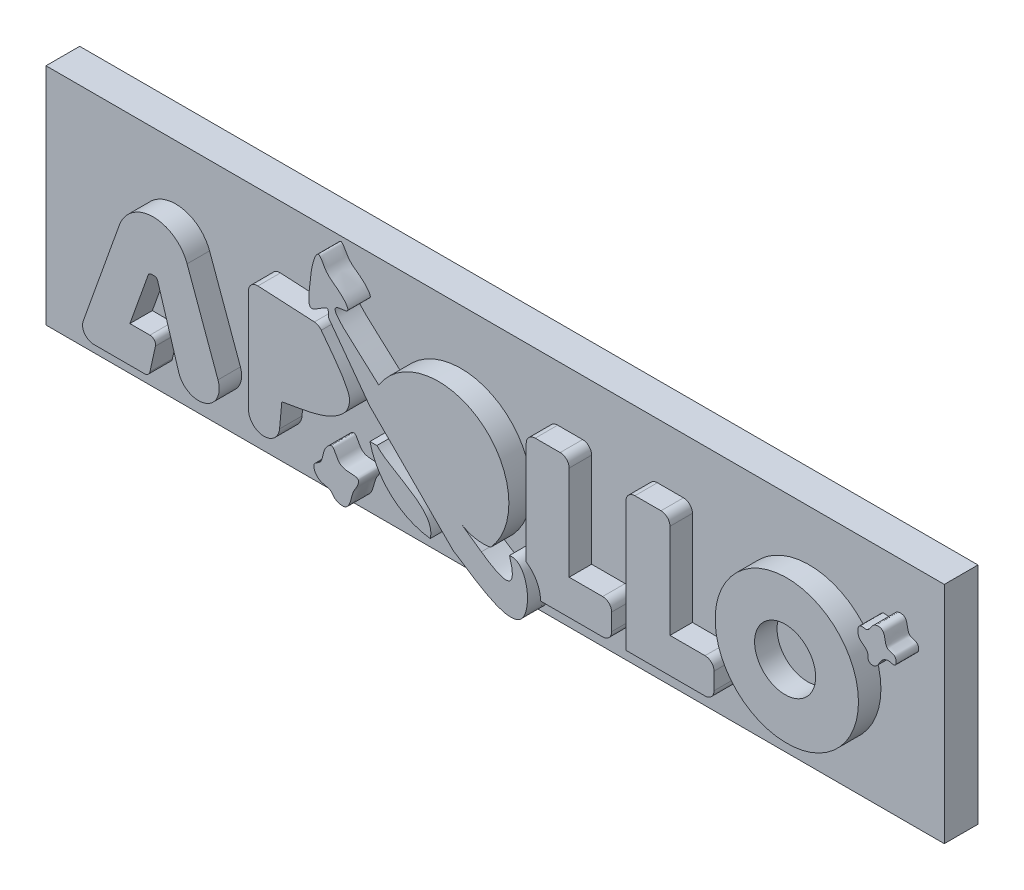
SolidWorks part; units mm, degrees
ref_plane "Front Plane" through (0, 0, 0) normal (0, 0, 1) x (1, 0, 0)
ref_plane "Top Plane" through (0, 0, 0) normal (0, 1, 0) x (1, 0, 0)
ref_plane "Right Plane" through (0, 0, 0) normal (1, 0, 0) x (0, 0, -1)
sketch "Sketch1" plane through (0, 0, 0) normal (0, 0, 1) x (1, 0, 0)
  line L1 (-40, 10) -> (40, 10)
  line L2 (-40, 10) -> (-40, -10)
  line L3 (-40, -10) -> (40, -10)
  line L4 (40, 10) -> (40, -10)
  line L5 (-40, 10) -> (40, -10) construction
  line L6 (-40, -10) -> (40, 10) construction
  point P0 (0, 0)
  dimension "D1" = 20
  dimension "D2" = 80
extrude "Boss-Extrude1" add sketch "Sketch1" along normal blind 3
sketch "Sketch2" plane through (0, 0, 3) normal (0, 0, 1) x (1, 0, 0)
  line L0 (190.2331, 305.278) -> (990.2331, 305.278) construction
  line L1 (27.6362, 109.7906) -> (244.3029, 109.7906) construction
  line L2 (-19.9678, 4.5009) -> (-13.7037, 4.1712)
  line L3 (-17.0006, -3.4116) -> (-17.3303, -7.0381)
  line L4 (-17.3303, -7.0381) -> (-19.9678, -6.7085)
  line L5 (-19.9678, -6.7085) -> (-19.9678, 4.5009)
  line L6 (-28.8278, -7.3662) -> (-35.1631, -7.3662)
  line L7 (-35.1631, -7.3662) -> (-30.7049, 5.1167)
  line L8 (-30.7049, 5.1167) -> (-26.1998, 5.1167)
  line L9 (-26.1998, 5.1167) -> (-21.7886, -7.0381)
  line L10 (-21.7886, -7.0381) -> (-25.7775, -7.0381)
  line L11 (-25.7775, -7.0381) -> (-28.1239, 0.6116)
  line L12 (-28.1239, 0.6116) -> (-28.8278, 0.6116)
  line L13 (-28.8278, 0.6116) -> (-30.5287, -4.1509)
  line L14 (-30.5287, -4.1509) -> (-28.1239, -4.1509)
  line L15 (-28.1239, -4.1509) -> (-28.8278, -7.3662)
  line L16 (-12.8172, 5.1167) -> (-9.1771, 0.1792)
  line L17 (-9.1771, 0.1792) -> (-1.7363, -7.2616)
  line L18 (0.7708, -6.1035) -> (-0.949, -4.8891)
  line L19 (4.7677, 5.0631) -> (8.5901, 5.0631)
  line L20 (8.5901, 5.0631) -> (8.5901, -4.1509)
  line L21 (8.5901, -4.1509) -> (12.3727, -4.1509)
  line L22 (12.3727, -4.1509) -> (12.3727, -7.2616)
  line L23 (12.3727, -7.2616) -> (6.0418, -7.2616)
  line L24 (4.7677, -4.8891) -> (4.7677, 5.0631)
  line L25 (13.6468, 5.0631) -> (13.6468, -7.2616)
  line L26 (13.6468, -7.2616) -> (21.4907, -7.2616)
  line L27 (21.4907, -7.2616) -> (21.4907, -4.1509)
  line L28 (21.4907, -4.1509) -> (17.5688, -4.1509)
  line L29 (17.5688, -4.1509) -> (17.5688, 5.0631)
  line L30 (17.5688, 5.0631) -> (13.6468, 5.0631)
  arc A0 (1.6039, -5.3346) -> (-8.365, 2.1874) centre (-3.0468, -1.1313) ccw
  arc A1 (-9.1771, 0.1792) -> (-1.7363, -7.2616) centre (-3.0468, -1.1313) ccw
  arc A2 (6.0418, -7.2616) -> (4.7677, -4.8891) centre (3.196, -7.2616) ccw
  circle A3 centre (27.8212, -0.8763) radius 2.7192
  circle A4 centre (27.9735, -0.8887) radius 6.381
  spline S0 degree 3 poles (-13.7037, 4.1712) (-12.8246, 2.8524) (-11.6697, 1.6805) (-11.0662, 0.215) (-10.8529, -0.3032) (-11.0236, -1.0147) (-11.3959, -1.4335) (-12.7133, -2.9156) (-15.3185, -3.0752) (-17.0006, -3.4116) knots 0 0 0 0 1 1 1 2 2 2 3 3 3 3
  spline S1 degree 3 poles (3.2781, -5.1299) (4.1587, -8.0055) (2.5693, -7.3735) (0.7708, -6.1035) knots 0 0 0 0 0.147053 0.147053 0.147053 0.147053
  spline S2 degree 3 poles (-8.5312, -2.5551) (-7.1149, -4.0344) (-3.2486, -5.0203) (-3.7795, -7.3571) knots 0 0 0 0 1 1 1 1
  spline S3 degree 1 poles (-8.5312, -2.5551) (-9.1517, -2.5551) knots 0 0 1 1
  spline S4 degree 3 poles (-1.7363, -7.2616) (-0.729, -7.8021) (5.8305, -13.1907) (4.9302, -4.8805) (3.2781, -5.1299) knots 0 0 0 0 0.585486 1 1 1 1
  spline S5 degree 3 poles (-8.365, 2.1874) (-8.9426, 2.7222) (-10.3611, 4.0014) (-13.1765, 6.4701) (-10.6701, 6.3535) (-12.0702, 7.9682) (-12.99, 8.2466) (-13.819, 10.2137) (-14.4191, 8.1055) (-14.4256, 7.0444) (-14.97, 4.053) (-12.6676, 6.4077) (-12.9041, 5.2317) (-12.7939, 5.0773) (-12.7777, 5.0631) knots 0.503916 0.503916 0.503916 0.503916 0.576099 0.651465 0.677045 0.710584 0.764881 0.792948 0.837231 0.87005 0.926524 0.97056 0.988496 0.990888 0.990888 0.990888 0.990888
  spline S6 degree 2 poles (-0.949, -4.8891) (0.259, -5.5831) (1.6039, -5.3346) knots 0 0 0 1 1 1
  spline S7 degree 3 poles (35.5396, 5.8714) (36.8772, 5.8667) (36.5558, 4.3308) (37.775, 4.409) (37.725, 3.3968) (37.0344, 3.7111) (36.2693, 3.4166) (36.0195, 2.4249) (35.1208, 2.6637) (35.3455, 3.6054) (34.1827, 3.8345) (34.2968, 5.2745) (35.3147, 4.8674) (35.5396, 5.8714) (36.8772, 5.8667) (36.5558, 4.3308) knots -0.214966 -0.16 -0.068707 0 0.129711 0.201373 0.260824 0.302302 0.374726 0.481659 0.525113 0.580837 0.697415 0.785034 0.84 0.931293 1 1.129711 1.201373 1.260824 only from (36.4574, 5.7328) to (36.4574, 5.7328)
  spline S8 degree 3 poles (-13.4599, -5.3408) (-12.3473, -4.1623) (-12.0452, -6.2784) (-9.8715, -5.5866) (-10.3105, -6.6704) (-10.8549, -7.3826) (-10.8307, -9.0287) (-12.281, -8.6539) (-12.7166, -7.8647) (-13.7688, -8.064) (-14.3804, -6.7478) (-13.2937, -6.3504) (-13.4599, -5.3408) (-12.3473, -4.1623) (-12.0452, -6.2784) knots -0.217717 -0.181179 -0.062931 0 0.110115 0.245487 0.297532 0.32939 0.480572 0.567582 0.595867 0.693752 0.782283 0.818821 0.937069 1 1.110115 1.245487 1.297532 only from (-12.5925, -4.6028) to (-12.5925, -4.6028)
extrude "Boss-Extrude2" add sketch "Sketch2" along normal blind 2 contours L15 L14 L13 L12 L11 L10 L9 L8 L7 L6 | S8 | L18 S6 A0 S5 L16 L17 S4 S1 | S2 S3 A1 | A2 L23 L22 L21 L20 L19 L24 | L29 L30 L25 L26 L27 L28 | A4 A3 | L3 L4 L5 L2 S0 | S7
fillet "Fillet2" radius 3.2051 4 edges at (-28.4524, 5.1167, 5) (-26.1998, 5.1167, 4) (-30.7049, 5.1167, 4) (-28.4524, 5.1167, 3)
fillet "Fillet3" radius 1 1 edges at (-35.1631, -7.3662, 4)
fillet "Fillet4" radius 0.5 2 edges at (-28.1239, -4.1509, 4) (-28.8278, -7.3662, 4)
fillet "Fillet5" radius 0.3 2 edges at (-28.1239, 0.6116, 4) (-28.8278, 0.6116, 4)
fillet "Fillet6" radius 1.8416 4 edges at (-23.783, -7.0381, 5) (-25.7775, -7.0381, 4) (-21.7886, -7.0381, 4) (-23.783, -7.0381, 3)
fillet "Fillet7" radius 1.3865 4 edges at (-18.649, -6.8733, 5) (-19.9678, -6.7085, 4) (-17.3303, -7.0381, 4) (-18.649, -6.8733, 3)
fillet "Fillet8" radius 0.8 2 edges at (-19.9678, 4.5009, 4) (-13.7037, 4.1712, 4)
fillet "Fillet9" radius 0.8 8 edges at (21.4907, -4.1509, 4) (21.4907, -7.2616, 4) (17.5688, 5.0631, 4) (13.6468, 5.0631, 4) (12.3727, -4.1509, 4) (12.3727, -7.2616, 4) (4.7677, 5.0631, 4) (8.5901, 5.0631, 4)
sketch "Orientation Sketch" plane through (0, 0, 3) normal (0, 0, 1) x (1, 0, 0)
  line L0 (-10.3758, -1.4647) -> (-10.3758, 2.6848) construction
  line L1 (-9.5337, 3.4837) -> (-7.6317, 3.3836) construction
  line L2 (-8.8922, -0.4283) -> (-8.9921, -1.5275) construction
  line L3 (-13.4803, -1.5908) -> (-14.3888, 1.3713) construction
  line L4 (-14.8769, 1.3842) -> (-15.6562, -0.7979) construction
  line L5 (-15.6562, -0.7979) -> (-15.0752, -0.7979) construction
  line L6 (-14.5867, -1.4048) -> (-14.7198, -2.0125) construction
  line L7 (-15.2082, -2.4056) -> (-16.5545, -2.4056) construction
  line L8 (-17.4962, -1.0692) -> (-16.1242, 2.7723) construction
  line L9 (-13.1086, 2.78) -> (-11.7344, -1.0066) construction
  line L10 (1.9919, -1.167) -> (1.9919, 3.0091) construction
  line L11 (2.7919, 3.8091) -> (3.1031, 3.8091) construction
  line L12 (3.9031, 3.0091) -> (3.9031, -0.7979) construction
  line L13 (3.9031, -0.7979) -> (4.9944, -0.7979) construction
  line L14 (4.9944, -2.3532) -> (2.629, -2.3532) construction
  line L15 (-0.0065, -1.7742) -> (-0.8664, -1.167) construction
  line L16 (-4.9804, 1.3671) -> (-1.2601, -2.3532) construction
  line L17 (-6.8005, 3.8359) -> (-4.9804, 1.3671) construction
  line L18 (40, -10) -> (40, 10) construction
  line L19 (40, 10) -> (-40, 10) construction
  line L20 (-40, 10) -> (-40, -10) construction
  line L21 (-40, -10) -> (40, -10) construction
  line L22 (-4.6575, 0) -> (-4.9678, 0) construction
  line L23 (7.5925, 3.8091) -> (7.2315, 3.8091) construction
  line L24 (8.3925, -0.7979) -> (8.3925, 3.0091) construction
  line L25 (9.5535, -0.7979) -> (8.3925, -0.7979) construction
  line L26 (6.4315, -2.3532) -> (9.5535, -2.3532) construction
  line L27 (6.4315, 3.0091) -> (6.4315, -2.3532) construction
  line L28 (-10.3758, -1.4647) -> (-10.3758, 2.6848)
  line L29 (-9.5337, 3.4837) -> (-7.6317, 3.3836)
  line L30 (-8.8922, -0.4283) -> (-8.9921, -1.5275)
  line L31 (-13.4803, -1.5908) -> (-14.3888, 1.3713)
  line L32 (-14.8769, 1.3842) -> (-15.6562, -0.7979)
  line L33 (-15.6562, -0.7979) -> (-15.0752, -0.7979)
  line L34 (-14.5867, -1.4048) -> (-14.7198, -2.0125)
  line L35 (-15.2082, -2.4056) -> (-16.5545, -2.4056)
  line L36 (-17.4962, -1.0692) -> (-16.1242, 2.7723)
  line L37 (-13.1086, 2.78) -> (-11.7344, -1.0066)
  line L38 (1.9919, -1.167) -> (1.9919, 3.0091)
  line L39 (2.7919, 3.8091) -> (3.1031, 3.8091)
  line L40 (3.9031, 3.0091) -> (3.9031, -0.7979)
  line L41 (3.9031, -0.7979) -> (4.9944, -0.7979)
  line L42 (4.9944, -2.3532) -> (2.629, -2.3532)
  line L43 (-0.0065, -1.7742) -> (-0.8664, -1.167)
  line L44 (-4.9804, 1.3671) -> (-1.2601, -2.3532)
  line L45 (-6.8005, 3.8359) -> (-4.9804, 1.3671)
  line L46 (40, -10) -> (40, 10) construction
  line L47 (40, 10) -> (-40, 10) construction
  line L48 (-40, 10) -> (-40, -10) construction
  line L49 (-40, -10) -> (40, -10) construction
  line L50 (-4.6575, 0) -> (-4.9678, 0)
  line L51 (7.5925, 3.8091) -> (7.2315, 3.8091)
  line L52 (8.3925, -0.7979) -> (8.3925, 3.0091)
  line L53 (9.5535, -0.7979) -> (8.3925, -0.7979)
  line L54 (6.4315, -2.3532) -> (9.5535, -2.3532)
  line L55 (6.4315, 3.0091) -> (6.4315, -2.3532)
  arc A0 (-10.3758, -1.4647) -> (-8.9921, -1.5275) centre (-9.6825, -1.4647) ccw construction
  arc A1 (-9.5337, 3.4837) -> (-10.3758, 2.6848) centre (-9.5758, 2.6848) ccw construction
  arc A2 (-7.0295, 3.059) -> (-7.6317, 3.3836) centre (-7.6737, 2.5847) ccw construction
  arc A3 (-13.4803, -1.5908) -> (-11.7344, -1.0066) centre (-12.5999, -1.3207) ccw construction
  arc A4 (-14.3888, 1.3713) -> (-14.635, 1.5806) centre (-14.6756, 1.2833) ccw construction
  arc A5 (-14.635, 1.5806) -> (-14.8769, 1.3842) centre (-14.5944, 1.2833) ccw construction
  arc A6 (-14.5867, -1.4048) -> (-15.0752, -0.7979) centre (-15.0752, -1.2979) ccw construction
  arc A7 (-15.2082, -2.4056) -> (-14.7198, -2.0125) centre (-15.2082, -1.9056) ccw construction
  arc A8 (-17.4962, -1.0692) -> (-16.5545, -2.4056) centre (-16.5545, -1.4056) ccw construction
  arc A9 (-13.1086, 2.78) -> (-16.1242, 2.7723) centre (-14.615, 2.2333) ccw construction
  circle A10 centre (13.5948, 0.8332) radius 3.1905 construction
  arc A11 (2.629, -2.3532) -> (1.9919, -1.167) centre (1.2061, -2.3532) ccw construction
  arc A12 (2.7919, 3.8091) -> (1.9919, 3.0091) centre (2.7919, 3.0091) ccw construction
  arc A13 (3.9031, 3.0091) -> (3.1031, 3.8091) centre (3.1031, 3.0091) ccw construction
  arc A14 (5.7941, -1.5756) -> (4.9944, -0.7979) centre (4.9944, -1.5979) ccw construction
  arc A15 (4.9944, -2.3532) -> (5.7941, -1.5756) centre (4.9944, -1.5532) ccw construction
  arc A16 (0.41, -1.3898) -> (-4.5744, 2.3713) centre (-1.9153, 0.7119) ccw construction
  arc A17 (-4.9678, 0) -> (-2.2817, -2.401) centre (-1.9153, 0.7119) ccw construction
  arc A18 (8.3925, 3.0091) -> (7.5925, 3.8091) centre (7.5925, 3.0091) ccw construction
  arc A19 (10.3531, -1.5756) -> (9.5535, -0.7979) centre (9.5535, -1.5979) ccw construction
  arc A20 (9.5535, -2.3532) -> (10.3531, -1.5756) centre (9.5535, -1.5532) ccw construction
  arc A21 (7.2315, 3.8091) -> (6.4315, 3.0091) centre (7.2315, 3.0091) ccw construction
  arc A22 (-10.3758, -1.4647) -> (-8.9921, -1.5275) centre (-9.6825, -1.4647) ccw
  arc A23 (-9.5337, 3.4837) -> (-10.3758, 2.6848) centre (-9.5758, 2.6848) ccw
  arc A24 (-7.0295, 3.059) -> (-7.6317, 3.3836) centre (-7.6737, 2.5847) ccw
  arc A25 (-13.4803, -1.5908) -> (-11.7344, -1.0066) centre (-12.5999, -1.3207) ccw
  arc A26 (-14.3888, 1.3713) -> (-14.635, 1.5806) centre (-14.6756, 1.2833) ccw
  arc A27 (-14.635, 1.5806) -> (-14.8769, 1.3842) centre (-14.5944, 1.2833) ccw
  arc A28 (-14.5867, -1.4048) -> (-15.0752, -0.7979) centre (-15.0752, -1.2979) ccw
  arc A29 (-15.2082, -2.4056) -> (-14.7198, -2.0125) centre (-15.2082, -1.9056) ccw
  arc A30 (-17.4962, -1.0692) -> (-16.5545, -2.4056) centre (-16.5545, -1.4056) ccw
  arc A31 (-13.1086, 2.78) -> (-16.1242, 2.7723) centre (-14.615, 2.2333) ccw
  circle A32 centre (13.5948, 0.8332) radius 3.1905
  arc A33 (2.629, -2.3532) -> (1.9919, -1.167) centre (1.2061, -2.3532) ccw
  arc A34 (2.7919, 3.8091) -> (1.9919, 3.0091) centre (2.7919, 3.0091) ccw
  arc A35 (3.9031, 3.0091) -> (3.1031, 3.8091) centre (3.1031, 3.0091) ccw
  arc A36 (5.7941, -1.5756) -> (4.9944, -0.7979) centre (4.9944, -1.5979) ccw
  arc A37 (4.9944, -2.3532) -> (5.7941, -1.5756) centre (4.9944, -1.5532) ccw
  arc A38 (0.41, -1.3898) -> (-4.5744, 2.3713) centre (-1.9153, 0.7119) ccw
  arc A39 (-4.9678, 0) -> (-2.2817, -2.401) centre (-1.9153, 0.7119) ccw
  arc A40 (8.3925, 3.0091) -> (7.5925, 3.8091) centre (7.5925, 3.0091) ccw
  arc A41 (10.3531, -1.5756) -> (9.5535, -0.7979) centre (9.5535, -1.5979) ccw
  arc A42 (9.5535, -2.3532) -> (10.3531, -1.5756) centre (9.5535, -1.5532) ccw
  arc A43 (7.2315, 3.8091) -> (6.4315, 3.0091) centre (7.2315, 3.0091) ccw
  parabola Q0 (-0.8664, -1.167) -> (0.41, -1.3898) focus (-0.0691, -0.5325) apex (-0.1957, -1.4041) construction
  parabola Q1 (-0.8664, -1.167) -> (0.41, -1.3898) focus (-0.0691, -0.5325) apex (-0.1957, -1.4041)
  spline S0 degree 3 poles (1739.9487, 976.3632) (-94.905, -15.7909) (-11.0255, 13.7718) (-5.925, 1.385) (-5.8184, 1.1259) (-5.9037, 0.7702) (-6.0899, 0.5608) (-14.102, -8.4528) (-117.3764, 80.3628) (1673.4025, -1082.014) knots -15.903911 -15.903911 -15.903911 -15.903911 1 1 1 2 2 2 14.163438 14.163438 14.163438 14.163438 only from (-7.0295, 3.059) to (-8.8922, -0.4283) construction
  spline S1 degree 3 poles (17.886, 3.443) (18.0467, 4.2109) (17.3779, 4.2133) (17.2654, 3.7112) (16.7565, 3.9148) (16.6994, 3.1948) (17.2808, 3.0802) (17.1685, 2.6094) (17.6178, 2.49) (17.7427, 2.9858) (18.1253, 3.1331) (18.4706, 2.9759) (18.4956, 3.482) (17.886, 3.443) (18.0467, 4.2109) (17.3779, 4.2133) knots -0.260824 -0.201373 -0.129711 0 0.068707 0.16 0.214966 0.302585 0.419163 0.474887 0.518341 0.625274 0.697698 0.739176 0.798627 0.870289 1 1.068707 1.16 1.214966 only from (17.8368, 4.1439) to (17.8368, 4.1439) construction
  spline S2 degree 3 poles (-1201.4821, 1596.6004) (1257.726, -1613.708) (-1278.5197, 1596.0039) (1260.0253, -1554.8569) knots -1.351503 -1.351503 -1.351503 -1.351503 1.696815 1.696815 1.696815 1.696815 only from (1.2471, -1.2874) to (-0.0065, -1.7742) construction
  spline S3 degree 3 poles (1226.9098, -1580.7489) (-95.2829, 142.7945) (68.664, -129.6415) (-43.3204, 104.6296) (-144.9479, -1995.5078) knots -4.231088 -4.231088 -4.231088 -4.231088 0.585486 4.369984 4.369984 4.369984 4.369984 only from (-1.2601, -2.3532) to (1.2471, -1.2874) construction
  spline S4 degree 3 poles (1474.1101, -1344.2134) (-90.1799, 73.0879) (12.0805, -12.2004) (-6.9802, 4.5126) (-5.727, 4.4543) (-6.427, 5.2617) (-6.8869, 5.4009) (-7.3014, 6.3844) (-7.6015, 5.3303) (-7.6047, 4.7997) (-7.8769, 3.304) (-3.2022, 8.0849) (-32.6795, -43.1634) (1173.3897, 1617.978) knots -1.667167 -1.667167 -1.667167 -1.667167 0.576099 0.651465 0.677045 0.710584 0.764881 0.792948 0.837231 0.87005 0.926524 0.97056 1.351031 1.351031 1.351031 1.351031 only from (-4.5744, 2.3713) to (-6.8005, 3.8359) construction
  spline S5 degree 3 poles (-6.4145, -1.8616) (-6.5656, -0.8036) (-7.1218, -1.3928) (-7.0388, -1.8976) (-7.5821, -2.0964) (-7.2763, -2.7545) (-6.7502, -2.6548) (-6.5324, -3.0494) (-5.8072, -3.2368) (-5.8194, -2.4138) (-5.5471, -2.0577) (-5.3276, -1.5158) (-6.4145, -1.8616) (-6.5656, -0.8036) (-7.1218, -1.3928) knots -0.297532 -0.245487 -0.110115 0 0.062931 0.181179 0.217717 0.306248 0.404133 0.432418 0.519428 0.67061 0.702468 0.754513 0.889885 1 1.062931 1.181179 1.217717 only from (-6.6882, -1.0239) to (-6.6882, -1.0239) construction
  spline S6 degree 3 poles (1924.8401, 526.1776) (-1967.0628, -515.7112) (1956.8377, 524.8921) (-1923.0105, -559.5476) knots -7.941387 -7.941387 -7.941387 -7.941387 8.644204 8.644204 8.644204 8.644204 only from (-4.6575, 0) to (-2.2817, -2.401) construction
  spline S7 degree 3 poles (-7.0295, 3.059) (-6.6307, 2.5173) (-6.1797, 2.0034) (-5.925, 1.385) (-5.8184, 1.1259) (-5.9037, 0.7702) (-6.0899, 0.5608) (-6.7486, -0.1802) (-8.0512, -0.26) (-8.8922, -0.4283) knots 0.156057 0.156057 0.156057 0.156057 1 1 1 2 2 2 3 3 3 3
  spline S8 degree 3 poles (17.886, 3.443) (18.0467, 4.2109) (17.3779, 4.2133) (17.2654, 3.7112) (16.7565, 3.9148) (16.6994, 3.1948) (17.2808, 3.0802) (17.1685, 2.6094) (17.6178, 2.49) (17.7427, 2.9858) (18.1253, 3.1331) (18.4706, 2.9759) (18.4956, 3.482) (17.886, 3.443) (18.0467, 4.2109) (17.3779, 4.2133) knots -0.260824 -0.201373 -0.129711 0 0.068707 0.16 0.214966 0.302585 0.419163 0.474887 0.518341 0.625274 0.697698 0.739176 0.798627 0.870289 1 1.068707 1.16 1.214966 only from (17.8368, 4.1439) to (17.8368, 4.1439)
  spline S9 degree 3 poles (1.2471, -1.2874) (1.6874, -2.7252) (0.8927, -2.4092) (-0.0065, -1.7742) knots 0 0 0 0 0.147053 0.147053 0.147053 0.147053
  spline S10 degree 3 poles (-1.2601, -2.3532) (-0.7564, -2.6235) (2.5233, -5.3178) (2.0732, -1.1627) (1.2471, -1.2874) knots 0 0 0 0 0.585486 1 1 1 1
  spline S11 degree 3 poles (-4.5744, 2.3713) (-4.8632, 2.6386) (-5.5725, 3.2783) (-6.9802, 4.5126) (-5.727, 4.4543) (-6.427, 5.2617) (-6.8869, 5.4009) (-7.3014, 6.3844) (-7.6015, 5.3303) (-7.6047, 4.7997) (-7.8769, 3.304) (-6.7257, 4.4814) (-6.8396, 3.9152) (-6.8005, 3.8359) knots 0.503916 0.503916 0.503916 0.503916 0.576099 0.651465 0.677045 0.710584 0.764881 0.792948 0.837231 0.87005 0.926524 0.97056 0.988496 0.988496 0.988496 0.988496
  spline S12 degree 3 poles (-6.4145, -1.8616) (-6.5656, -0.8036) (-7.1218, -1.3928) (-7.0388, -1.8976) (-7.5821, -2.0964) (-7.2763, -2.7545) (-6.7502, -2.6548) (-6.5324, -3.0494) (-5.8072, -3.2368) (-5.8194, -2.4138) (-5.5471, -2.0577) (-5.3276, -1.5158) (-6.4145, -1.8616) (-6.5656, -0.8036) (-7.1218, -1.3928) knots -0.297532 -0.245487 -0.110115 0 0.062931 0.181179 0.217717 0.306248 0.404133 0.432418 0.519428 0.67061 0.702468 0.754513 0.889885 1 1.062931 1.181179 1.217717 only from (-6.6882, -1.0239) to (-6.6882, -1.0239)
  spline S13 degree 3 poles (-4.6575, 0) (-3.9494, -0.7397) (-2.0162, -1.2326) (-2.2817, -2.401) knots 0 0 0 0 1 1 1 1
  point P12 (0, 0)
other "FormTool1"
